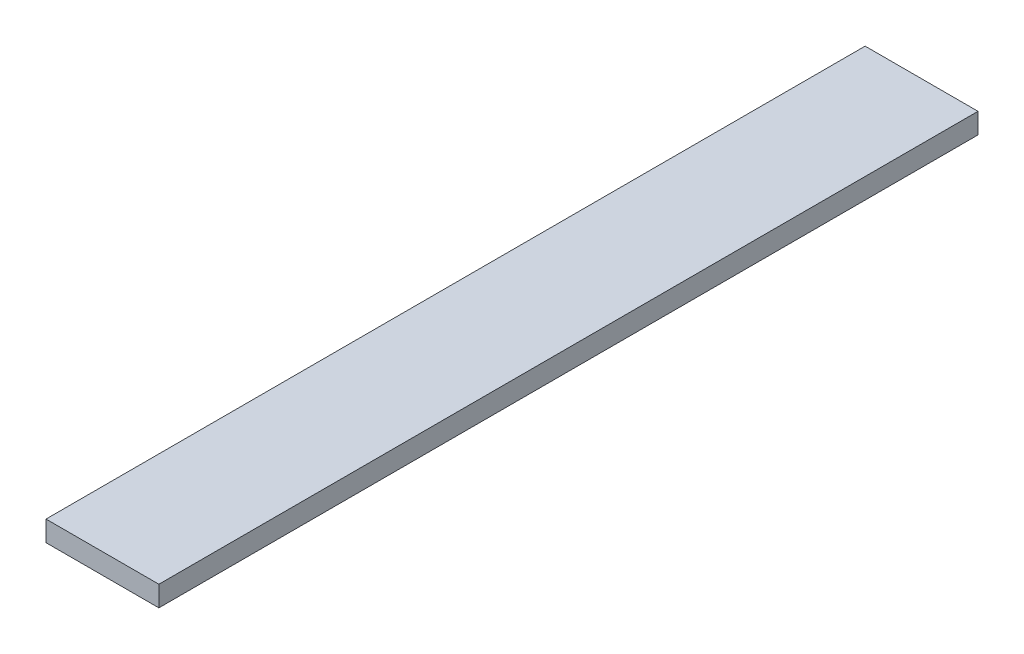
SolidWorks part; units mm, degrees
ref_plane "Front Plane" through (0, 0, 0) normal (0, 0, 1) x (1, 0, 0)
ref_plane "Top Plane" through (0, 0, 0) normal (0, 1, 0) x (1, 0, 0)
ref_plane "Right Plane" through (0, 0, 0) normal (1, 0, 0) x (0, 0, -1)
sketch "Sketch2" plane through (0, 0, 0) normal (0, 1, 0) x (1, 0, 0)
  line L0 (0, 0) -> (35, 0)
  line L1 (35, 0) -> (35, 254)
  line L2 (35, 254) -> (0, 254)
  line L3 (0, 254) -> (0, 0)
  dimension "D1" = 35
  dimension "D2" = 254
extrude "Boss-Extrude1" add sketch "Sketch2" along normal blind 6.35
equation "\"wall_thickness\" = 0.125in"
equation "\"base_thickness\" = 0.25in"
equation "\"D1@Boss-Extrude1\"=\"base_thickness\""
